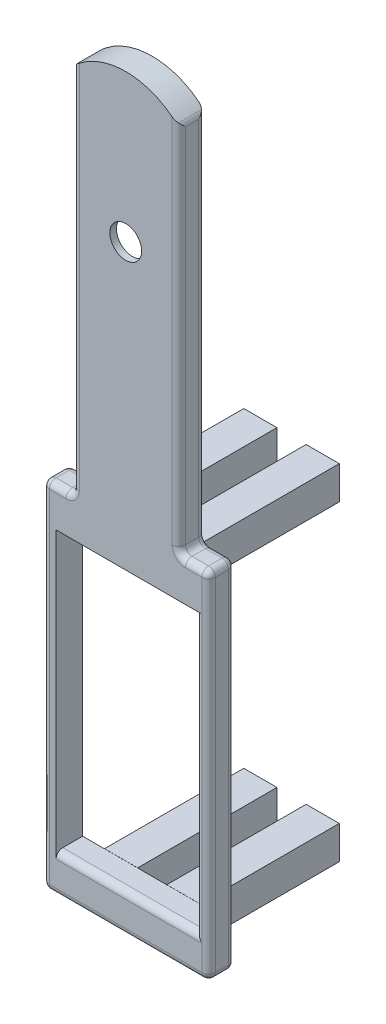
SolidWorks part; units mm, degrees
ref_plane "前基準面" through (0, 0, 0) normal (0, 0, 1) x (1, 0, 0)
ref_plane "上基準面" through (0, 0, 0) normal (0, 1, 0) x (1, 0, 0)
ref_plane "右基準面" through (0, 0, 0) normal (1, 0, 0) x (0, 0, -1)
sketch "草圖1" plane through (0, 0, 0) normal (0, 0, 1) x (1, 0, 0)
  line L0 (0, 30.5889) -> (0, -26.6295) construction
  line L1 (0, -55) -> (0, 55) construction
  line L2 (-30.3792, 0) -> (34.0344, 0) construction
  line L3 (55, 0) -> (-55, 0) construction
  line L4 (-12.5, 26.8) -> (-12.5, -26.8)
  line L5 (-12.5, -26.8) -> (12.5, -26.8)
  line L6 (-12.5, 26.8) -> (-8, 26.8)
  line L7 (-8, 26.8) -> (-8, 82.8)
  line L8 (12.5, 26.8) -> (12.5, -26.8)
  line L9 (12.5, 26.8) -> (8, 26.8)
  line L10 (8, 26.8) -> (8, 82.8)
  arc A3 (-8, 82.8) -> (8, 82.8) centre (0, 74.8) cw
  point P17 (0, -26.8)
  dimension "D1" = 53.6
  dimension "D2" = 26.8
  dimension "D3" = 25
  dimension "D4" = 56
  dimension "D5" = 4.5
sketch "草圖2" plane through (0, 0, 0) normal (0, 0, 1) x (1, 0, 0)
  line L0 (-7.2277, 0) -> (8.5378, 0) construction
  line L1 (-30.3792, 0) -> (34.0344, 0) construction
  line L2 (0, 16.7549) -> (0, -11.0092) construction
  line L3 (0, 30.5889) -> (0, -26.6295) construction
  line L5 (-10.5, 21) -> (10.5, 21)
  line L6 (-10.5, 21) -> (-10.5, -21)
  line L7 (-10.5, -21) -> (10.5, -21)
  line L8 (10.5, 21) -> (10.5, -21)
  dimension "D1" = 21
  dimension "D2" = 42
  dimension "D3" = 10.5
  dimension "D4" = 21
sketch "草圖3" plane through (0, 0, 0) normal (0, 0, 1) x (1, 0, 0)
  line L0 (-10.5417, 0) -> (11.1356, 0) construction
  line L1 (-30.3792, 0) -> (34.0344, 0) construction
  line L2 (0, 27.3744) -> (0, -17.8194) construction
  line L3 (0, 30.5889) -> (0, -26.6295) construction
  line L4 (-10.5, 21) -> (10.5, 21) construction
  circle A0 centre (-4.7, 23.81) radius 1.15
  circle A1 centre (4.7, 23.81) radius 1.15
  circle A2 centre (4.7, -23.81) radius 1.15
  circle A3 centre (-4.7, -23.81) radius 1.15
  dimension "D2" = 5.8
  dimension "D3" = 2.3
  dimension "D4" = 2.81
  dimension "D5" = 2.81
  dimension "D6" = 2.3
  dimension "D7" = 2.3
  dimension "D8" = 2.3
  dimension "D1" = 5.8
sketch "草圖4" plane through (0, 0, 0) normal (0, 0, 1) x (1, 0, 0)
  line L1 (0, -62.1025) -> (0, 62.1025) construction
  line L2 (-2.6, 81.8) -> (-5, 68.0072)
  line L3 (2.6, 81.8) -> (5, 68.0072)
  line L4 (-2.6, 47.0982) -> (-5.7101, 60.7484)
  line L5 (2.6, 47.0982) -> (5.7101, 60.7484)
  arc A0 (2.6, 81.8) -> (-2.6, 81.8) centre (0, 81.8) ccw
  arc A1 (-5, 68.0072) -> (-5.7101, 60.7484) centre (0, 63.8539) ccw
  arc A2 (-2.6, 47.0982) -> (2.6, 47.0982) centre (0, 47.0982) ccw
  arc A3 (5.7101, 60.7484) -> (5, 68.0072) centre (0, 63.8539) ccw
  dimension "D1" = 13
  dimension "D7" = 55
  dimension "D2" = 2.6
  dimension "D3" = 5
  dimension "D4" = 5
  dimension "D5" = 2.6
  dimension "D6" = 14
sketch "草圖5" plane through (0, 0, 0) normal (0, 0, 1) x (1, 0, 0)
  circle A0 centre (0, 63.8539) radius 2.4
  dimension "D1" = 4.8
sketch "草圖6" plane through (0, 0, 0) normal (0, 0, 1) x (1, 0, 0)
  line L0 (-10.5417, 0) -> (11.1356, 0) construction
  line L1 (0, 27.3744) -> (0, -21.0233) construction
  line L2 (0, 30.5889) -> (0, -26.6295) construction
  line L3 (-10.5, 21) -> (10.5, 21) construction
  line L4 (-7.2, 26) -> (-2.2, 26)
  line L5 (-7.2, 26) -> (-7.2, 21)
  line L6 (-7.2, 21) -> (-2.2, 21)
  line L7 (-2.2, 26) -> (-2.2, 21)
  line L8 (7.2, -25.9851) -> (2.2, -25.9851)
  line L13 (2.2, -20.9851) -> (2.2, -25.9851)
  line L14 (7.2, -20.9851) -> (2.2, -20.9851)
  line L15 (-7.2, -20.9851) -> (-2.2, -20.9851)
  line L16 (-7.2, -20.9851) -> (-7.2, -25.9851)
  line L17 (-7.2, -25.9851) -> (-2.2, -25.9851)
  line L18 (-2.2, -20.9851) -> (-2.2, -25.9851)
  line L19 (7.2, -20.9851) -> (7.2, -25.9851)
  line L20 (7.2, 21) -> (2.2, 21)
  line L21 (2.2, 26) -> (2.2, 21)
  line L22 (7.2, 26) -> (2.2, 26)
  line L23 (7.2, 26) -> (7.2, 21)
  dimension "D1" = 5
  dimension "D2" = 5
  dimension "D3" = 3.3
  dimension "D4" = 5
  dimension "D5" = 5
  dimension "D6" = 3.3
extrude "填料-伸長1" add sketch "草圖1" along normal blind 4
extrude "除料-伸長2" cut sketch "草圖4" along normal blind 3 contours L5 A3 L3 A0 L2 A1 L4 A2
extrude "除料-伸長5" cut sketch "草圖5" along normal blind 4 and the other way blind 2 contours A0
extrude "除料-伸長6" cut sketch "草圖2" along normal blind 4 contours L5 L8 L7 L6
extrude "填料-伸長2" add sketch "草圖6" against normal blind 21
extrude "除料-伸長7" cut sketch "草圖3" against normal blind 21
fillet "圓角3" radius 1 9 edges at (12.5, 0, 4) (12.5, 26.8, 2) (12.5, 0, 0) (-12.5, -26.8, 2) (0, -26.8, 4) (12.5, -26.8, 2) (0, -26.8, 0) (0, -21, 4) (10.5, 0, 4)
fillet "圓角5" radius 1 10 edges at (-8, 54.8, 4) (-8, 54.8, 0) (-12.2071, -26.5071, 3.7071) (-12.2071, -26.5071, 0.2929) (-12.5, 0.5, 4) (-12.5, 0.5, 0) (-8, 26.8, 2) (-10.25, 26.8, 4) (-12.5, 26.8, 2) (-10.25, 26.8, 0)
fillet "圓角6" radius 1 8 edges at (12.2071, 26.5071, 0.2929) (12.2071, 26.5071, 3.7071) (9.75, 26.8, 0) (9.75, 26.8, 4) (8, 26.8, 2) (8, 54.8, 4) (8, 82.8, 2) (8, 54.8, 0)
